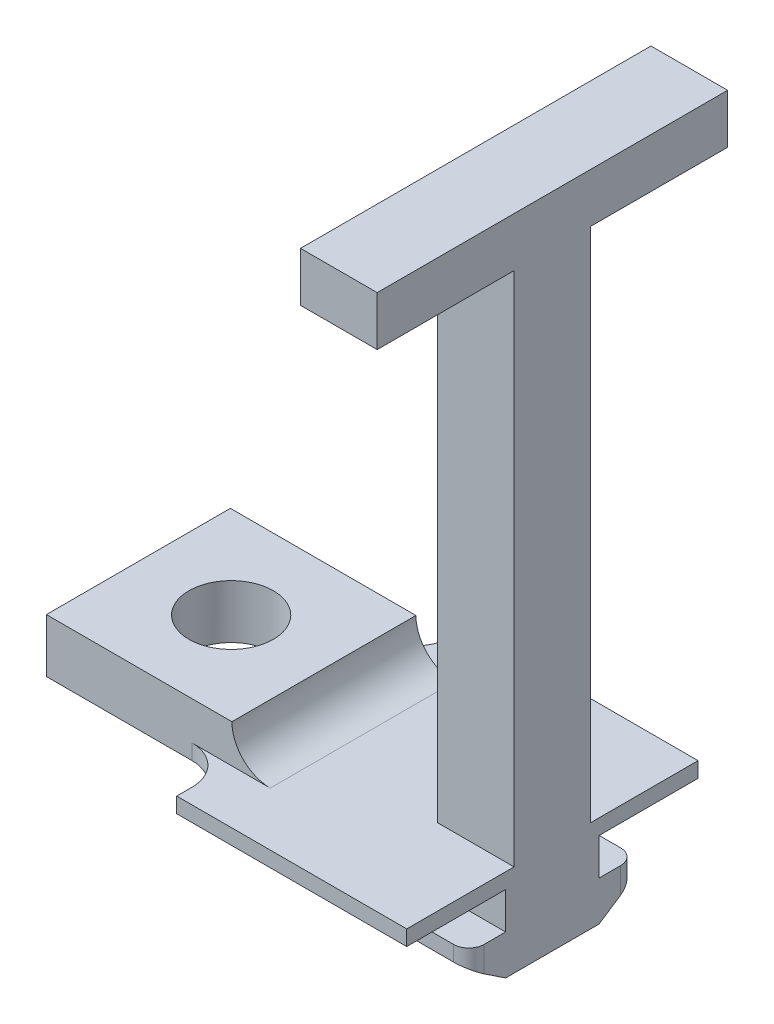
SolidWorks part; units mm, degrees
ref_plane "Front Plane" through (0, 0, 0) normal (0, 0, 1) x (1, 0, 0)
ref_plane "Top Plane" through (0, 0, 0) normal (0, 1, 0) x (1, 0, 0)
ref_plane "Right Plane" through (0, 0, 0) normal (1, 0, 0) x (0, 0, -1)
sketch "Sketch1" plane through (0, 0, 0) normal (1, 0, 0) x (0, 0, -1)
  line L1 (-11.4272, 1.6102) -> (11.4272, 1.6102)
  line L2 (-11.4272, 1.6102) -> (-11.4272, -1.6102)
  line L3 (-11.4272, -1.6102) -> (11.4272, -1.6102)
  line L4 (11.4272, 1.6102) -> (11.4272, -1.6102)
  line L5 (-11.4272, 1.6102) -> (11.4272, -1.6102) construction
  line L6 (-11.4272, -1.6102) -> (11.4272, 1.6102) construction
  point P0 (0, 0)
extrude "Boss-Extrude1" add sketch "Sketch1" against normal blind 5 contours L2 L1 L4 L3
sketch "Sketch2" plane through (0, 0, 0) normal (1, 0, 0) x (0, 0, -1)
  line L0 (0, -36.2873) -> (0, 1.6102) construction
  line L5 (-2.5, -36.2873) -> (2.5, -36.2873)
  line L6 (2.5, -36.2873) -> (2.5, 1.6102)
  line L7 (-2.5, -36.2873) -> (-2.5, 1.6102)
  line L8 (2.5, -17.3385) -> (-2.5, -17.3385) construction
  line L9 (-2.5, 1.6102) -> (2.5, 1.6102)
  line L11 (-11.4272, 1.6102) -> (11.4272, 1.6102) construction
  point P2 (0, 0)
  point P3 (0, 0)
  point P4 (0, 0)
  point P5 (0, 0)
  point P6 (0, 0)
  point P10 (0, 0)
  point P16 (-13.5643, -2.0375)
  point P17 (0, 0)
  point P18 (0, 0)
  point P19 (0, 0)
  dimension "D1" = 5
extrude "Boss-Extrude2" add sketch "Sketch2" against normal blind 5
sketch "Sketch3" plane through (0, 0, 0) normal (1, 0, 0) x (0, 0, -1)
  line L1 (-2.5, -36.2873) -> (2.5, -36.2873) construction
  line B0 (0, -41.2873) -> (0, -36.2873) construction
  line B1 (-9.5, -36.2873) -> (-9.5, -35.2873)
  line B2 (-3.05, -36.2873) -> (3.05, -36.2873) construction
  line B3 (-3.05, -36.2873) -> (-3.05, -38.6873)
  line B4 (3.05, -36.2873) -> (3.05, -38.6873)
  line B5 (-3.05, -38.6873) -> (-5.45, -38.6873)
  line B6 (-5.45, -38.6873) -> (-5.45, -39.6873)
  line B7 (3.05, -38.6873) -> (5.45, -38.6873)
  line B8 (5.45, -38.6873) -> (5.45, -39.6873)
  line B9 (-3.05, -36.2873) -> (-9.5, -36.2873)
  line B10 (-9.5, -35.2873) -> (9.5, -35.2873)
  line B11 (3.05, -36.2873) -> (9.5, -36.2873)
  line B12 (9.5, -35.2873) -> (9.5, -36.2873)
  line B13 (-3.05, -38.6873) -> (-3.05, -41.2873) construction
  line B14 (-5.45, -39.6873) -> (-3.05, -41.2873)
  line B15 (3.05, -38.6873) -> (3.05, -41.2873) construction
  line B16 (5.45, -39.6873) -> (3.05, -41.2873)
  line B17 (3.05, -41.2873) -> (-3.05, -41.2873)
sketch_block_instance "Block-2020 rail insert-1"
sketch_block "Block-2020 rail insert" parameters "D1"=5, "D2"=6.1, "D3"=2.4, "D4"=2.4, "D5"=1, "D6"=1, "D7"=19
extrude "Boss-Extrude3" add sketch "Sketch3" against normal blind 15
fillet "Fillet1" radius 1 2 edges at (0, -39.1873, 5.45) (0, -39.1873, -5.45)
sketch "Sketch38" plane through (-15, 0, 0) normal (-1, 0, 0) x (0, 0, 1)
  line L3 (-6, -32.7873) -> (6, -32.7873)
  line L4 (-6, -32.7873) -> (-6, -36.2873)
  line L5 (-6, -36.2873) -> (6, -36.2873)
  line L6 (6, -32.7873) -> (6, -36.2873)
  line L7 (-6, -32.7873) -> (6, -36.2873) construction
  line L8 (-6, -36.2873) -> (6, -32.7873) construction
  line L9 (3.05, -36.2873) -> (-3.05, -36.2873) construction
  line L10 (0, -36.2873) -> (0, -34.5373) construction
  point P4 (0, -34.5373)
  point P5 (0, 0)
  dimension "D1" = 12
  dimension "D2" = 3.5
extrude "Boss-Extrude28" add sketch "Sketch38" along normal blind 12 and the other way blind 0.1
sketch "Sketch39" plane through (0, -32.7873, 0) normal (0, 1, 0) x (1, 0, 0)
  line L0 (-27, -6) -> (-14.9, 6) construction
  circle A0 centre (-20.95, 0) radius 2.75
  dimension "D1" = 5.5
extrude "Cut-Extrude3" cut sketch "Sketch39" against normal up to next contours A0
ref_axis "Axis1" through (0, -36.2873, 0) along (1, 0, 0)
fillet "Fillet2" radius 2.5 3 edges at (-14.9, -35.2873, 0) (-15, -35.7873, -6) (-15, -35.7873, 6)
sketch "Sketch40" plane through (0, 1.6102, 0) normal (0, 1, 0) x (1, 0, 0)
  line L0 (0, 11.4272) -> (-5, -11.4272) construction
  line L1 (-27.5, 40) -> (22.5, 40)
  line L2 (-27.5, 40) -> (-27.5, -40)
  line L3 (-27.5, -40) -> (22.5, -40)
  line L4 (22.5, 40) -> (22.5, -40)
  line L5 (-27.5, 40) -> (22.5, -40) construction
  line L6 (-27.5, -40) -> (22.5, 40) construction
  line L7 (-5, -11.4272) -> (0, -11.4272) construction
  line L8 (-5, -11.4272) -> (-5, 11.4272) construction
  point P0 (-2.5, 0)
  point P10 (0, 0)
  point P11 (-5, -11.4272)
  point P14 (0, 0)
  dimension "D1" = 50
  dimension "D2" = 80
